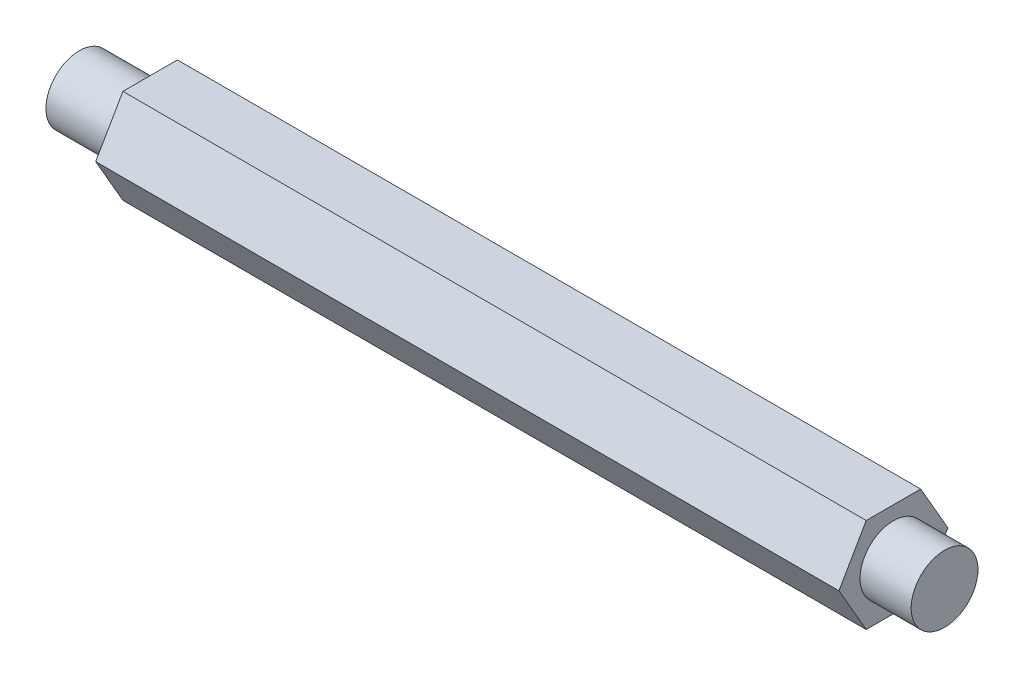
SolidWorks part; units mm, degrees
material "1060 Alloy"
ref_plane "Front Plane" through (0, 0, 0) normal (0, 0, 1) x (1, 0, 0)
ref_plane "Top Plane" through (0, 0, 0) normal (0, 1, 0) x (1, 0, 0)
ref_plane "Right Plane" through (0, 0, 0) normal (1, 0, 0) x (0, 0, -1)
sketch "Sketch1" plane through (0, 0, 0) normal (1, 0, 0) x (0, 0, -1)
  line L1 (6.9282, 0) -> (3.4641, 6)
  line L2 (3.4641, 6) -> (-3.4641, 6)
  line L3 (-3.4641, 6) -> (-6.9282, 0)
  line L4 (-6.9282, 0) -> (-3.4641, -6)
  line L5 (-3.4641, -6) -> (3.4641, -6)
  line L6 (3.4641, -6) -> (6.9282, 0)
  circle A0 centre (0, 0) radius 6 construction
  dimension "D1" = 12
extrude "Boss-Extrude1" add sketch "Sketch1" along normal blind 110
sketch "Sketch2" plane through (110, 0, 0) normal (1, 0, 0) x (0, 0, -1)
  circle A0 centre (0, 0) radius 4.25
  dimension "D1" = 8.5
extrude "Cut-Extrude1" cut sketch "Sketch2" against normal blind 6.5 flip side to cut
extrude "Cut-Extrude2" cut sketch "Sketch2<2>" along normal blind 9 from surface flip side to cut starting at face at (0, 0, 0)
sketch "Sketch2<2>" plane through (110, 0, 0) normal (1, 0, 0) x (0, 0, -1) same geometry as "Sketch2"
